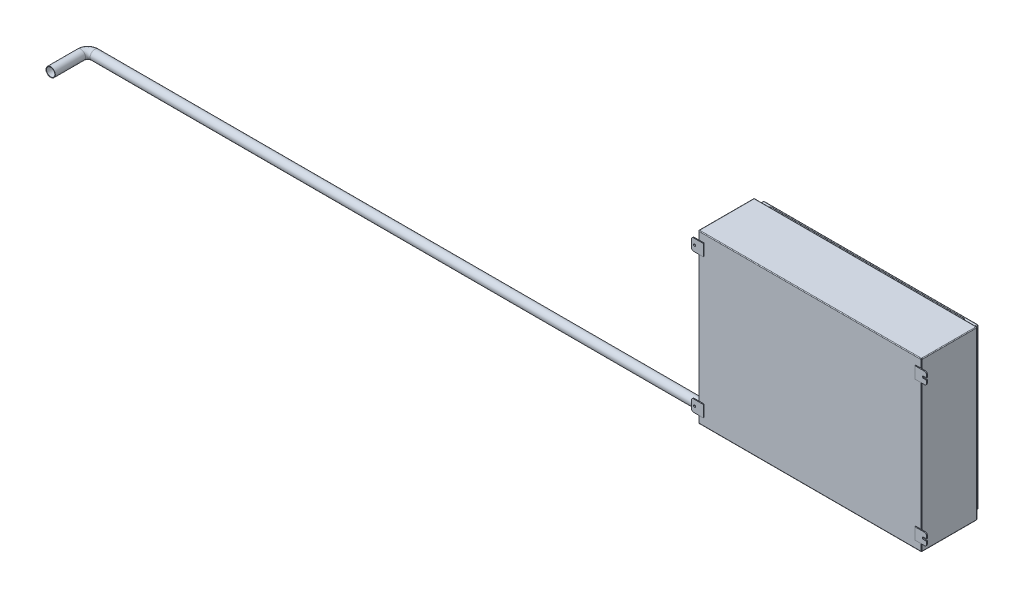
SolidWorks part; units mm, degrees
ref_plane "Front Plane" through (0, 0, 0) normal (0, 0, 1) x (1, 0, 0)
ref_plane "Top Plane" through (0, 0, 0) normal (0, 1, 0) x (1, 0, 0)
ref_plane "Right Plane" through (0, 0, 0) normal (1, 0, 0) x (0, 0, -1)
sketch "Sketch1" plane through (0, 0, 0) normal (0, 0, 1) x (1, 0, 0)
  line L0 (-609.6, -457.2) -> (609.6, 457.2) construction
  line L1 (-609.6, 457.2) -> (609.6, 457.2)
  line L2 (-609.6, 457.2) -> (-609.6, -457.2)
  line L3 (-609.6, -457.2) -> (609.6, -457.2)
  line L4 (609.6, 457.2) -> (609.6, -457.2)
  line L5 (-607.7026, 455.3026) -> (-607.7026, -455.3026)
  line L6 (-607.7026, -455.3026) -> (607.7026, -455.3026)
  line L7 (607.7026, 455.3026) -> (607.7026, -455.3026)
  line L8 (-607.7026, 455.3026) -> (607.7026, 455.3026)
  line L9 (571.5, -419.1) -> (-571.5, 419.1) construction
  line L10 (-571.5, 419.1) -> (571.5, 419.1)
  line L11 (-571.5, 419.1) -> (-571.5, -419.1)
  line L12 (-571.5, -419.1) -> (571.5, -419.1)
  line L13 (571.5, 419.1) -> (571.5, -419.1)
  line L14 (-549.275, 396.875) -> (-549.275, -396.875) construction
  line L15 (-549.275, -396.875) -> (549.275, -396.875) construction
  line L16 (549.275, 396.875) -> (549.275, -396.875) construction
  line L17 (-549.275, 396.875) -> (549.275, 396.875) construction
  line L18 (609.6, 412.75) -> (641.35, 412.75)
  line L19 (641.35, 412.75) -> (641.35, 386.5562)
  line L21 (-641.35, 349.25) -> (-609.6, 349.25)
  line L22 (0, 0) -> (0, 396.875) construction
  line L23 (-609.6, 412.75) -> (-641.35, 412.75)
  line L25 (-641.35, 412.75) -> (-641.35, 349.25)
  line L26 (0, 0) -> (0, 125.3343) construction
  line L27 (-544.5125, 396.875) -> (-544.5125, -396.875) construction
  line L28 (625.475, 375.4437) -> (609.6, 375.4437) construction
  line L29 (-625.475, 381) -> (-625.475, 349.25) construction
  line L30 (641.35, 349.25) -> (609.6, 349.25)
  line L31 (625.475, 375.4437) -> (641.35, 375.4437)
  line L32 (625.475, 386.5562) -> (641.35, 386.5562)
  line L33 (641.35, 375.4437) -> (641.35, 349.25)
  line L34 (625.475, 381) -> (625.475, 412.75) construction
  line L35 (-625.475, 365.125) -> (-609.6, 365.125) construction
  line L36 (0, 0) -> (571.5, 0) construction
  line L37 (-625.475, 381) -> (625.475, 381) construction
  line L38 (-641.35, -349.25) -> (-609.6, -349.25)
  line L39 (-641.35, -412.75) -> (-641.35, -349.25)
  line L40 (-609.6, -412.75) -> (-641.35, -412.75)
  line L41 (641.35, -349.25) -> (609.6, -349.25)
  line L42 (641.35, -375.4437) -> (641.35, -349.25)
  line L43 (625.475, -375.4437) -> (641.35, -375.4437)
  line L44 (641.35, -412.75) -> (641.35, -386.5562)
  line L45 (625.475, -386.5562) -> (641.35, -386.5562)
  line L46 (609.6, -412.75) -> (641.35, -412.75)
  circle A0 centre (549.275, 396.875) radius 4.7625 construction
  circle A1 centre (549.275, -396.875) radius 4.7625 construction
  circle A2 centre (-549.275, -396.875) radius 4.7625 construction
  circle A3 centre (-549.275, 396.875) radius 4.7625 construction
  circle A4 centre (-625.475, 381) radius 5.5563
  arc A6 (625.475, 386.5562) -> (625.475, 375.4437) centre (625.475, 381) ccw
  circle A12 centre (-625.475, -381) radius 5.5563
  arc A13 (625.475, -386.5562) -> (625.475, -375.4437) centre (625.475, -381) cw
  circle A14 centre (0, 396.875) radius 4.7625 construction
  circle A15 centre (0, -396.875) radius 4.7625 construction
  dimension "panel screw hole" = 9.525
  dimension "D6" = 11.1125
  dimension "D1" = 63.5
  dimension "D3" = 1250.95
  dimension "D2" = 22.225
sketch "Sketch2" plane through (0, 0, 0) normal (0, 1, 0) x (1, 0, 0)
  line L0 (-609.6, -152.4) -> (609.6, 152.4) construction
  line L1 (-609.6, 152.4) -> (609.6, 152.4)
  line L2 (-609.6, 152.4) -> (-609.6, -152.4)
  line L3 (-609.6, -152.4) -> (609.6, -152.4)
  line L4 (609.6, 152.4) -> (609.6, -152.4)
  line L5 (-607.7026, 150.5026) -> (-607.7026, -150.5026)
  line L6 (-571.5, -122.8166) -> (571.5, -122.8166)
  line L7 (-571.5, -122.8166) -> (-571.5, -125.4735)
  line L8 (-571.5, -125.4735) -> (571.5, -125.4735)
  line L9 (571.5, -122.8166) -> (571.5, -125.4735)
  line L10 (-607.7026, -150.5026) -> (607.7026, -150.5026)
  line L11 (607.7026, 150.5026) -> (607.7026, -150.5026)
  line L12 (-607.7026, 150.5026) -> (607.7026, 150.5026)
  line L13 (-609.6, 152.4) -> (609.6, 152.4) construction
  line L14 (-574.675, 152.4) -> (-574.675, 150.5026) construction
  line L15 (574.675, 152.4) -> (574.675, 150.5026) construction
  line L16 (-586.613, 173.482) -> (586.613, 173.482) construction
  line L17 (0, 0) -> (0, 173.482) construction
  line L18 (-586.613, 179.9666) -> (586.613, 179.9666) construction
  line L19 (-577.85, -152.4) -> (577.85, -152.4) construction
  line L20 (-641.35, -152.4) -> (-577.85, -152.4)
  line L21 (-641.35, -152.4) -> (-641.35, -157.226)
  line L22 (-641.35, -157.226) -> (-577.85, -157.226)
  line L23 (-577.85, -152.4) -> (-577.85, -157.226)
  line L24 (577.85, -152.4) -> (641.35, -152.4)
  line L25 (577.85, -152.4) -> (577.85, -157.226)
  line L26 (577.85, -157.226) -> (641.35, -157.226)
  line L27 (641.35, -152.4) -> (641.35, -157.226)
  line L28 (0, 0) -> (0, -152.4) construction
  line L29 (-586.613, 181.864) -> (586.613, 181.864) construction
  line L30 (-577.0499, 152.4) -> (-577.0499, 150.5026) construction
  dimension "D4" = 34.925
  dimension "P" = 1173.226
  dimension "D6" = 4.826
  dimension "D2" = 27.686
  dimension "D7" = 1.8974
  dimension "D8" = 29.464
  dimension "D9" = 63.5
  dimension "D10" = 32.5501
  dimension "D3" = 34.925
  dimension "D5" = 21.082
  dimension "D1" = 1.8974
sketch "Sketch4" plane through (0, 0, 0) normal (0, 0, 1) x (1, 0, 0)
  line L1 (-609.6, -457.2) -> (609.6, -457.2) construction
  line L2 (609.6, 457.2) -> (609.6, -457.2) construction
  line L4 (-609.6, 457.2) -> (609.6, 457.2) construction
  line L7 (-609.6, 457.2) -> (-609.6, -457.2) construction
  line L9 (-609.6, -457.2) -> (609.6, -457.2)
  line L10 (609.6, 457.2) -> (609.6, -457.2)
  line L12 (-609.6, 457.2) -> (609.6, 457.2)
  line L15 (-609.6, 457.2) -> (-609.6, -457.2)
extrude "Extrude1" add sketch "Sketch4" along normal mid plane 304.8
sketch "Sketch27" plane through (0, 0, -152.4) normal (0, 0, -1) x (-1, 0, 0)
  line L0 (609.6, 457.2) -> (609.6, -457.2) construction
  line L1 (574.675, -422.275) -> (-574.675, -422.275) construction
  line L2 (574.675, -422.275) -> (574.675, 422.275) construction
  line L3 (574.675, 422.275) -> (-574.675, 422.275) construction
  line L4 (-574.675, -422.275) -> (-574.675, 422.275) construction
  line L5 (609.6, 457.2) -> (-609.6, 457.2) construction
  line L10 (609.6, -457.2) -> (-609.6, -457.2) construction
  line L11 (578.4698, -426.0698) -> (-578.4698, -426.0698)
  line L12 (-578.4698, -426.0698) -> (-578.4698, 426.0698)
  line L13 (578.4698, 426.0698) -> (-578.4698, 426.0698)
  line L14 (578.4698, -426.0698) -> (578.4698, 426.0698)
  dimension "D1" = 34.925
  dimension "D2" = 34.925
  dimension "D3" = 34.925
  dimension "D4" = 3.7948
extrude "Extrude19" add sketch "Sketch27" along normal up to vertex (21.082 mm away) up to point (586.613, 0, -173.482)
fillet "Fillet1" radius 3.7948 20 edges at (609.6, -457.2, 0) (0, -457.2, -152.4) (609.6, 0, -152.4) (609.6, 0, 152.4) (0, -457.2, 152.4) (609.6, 457.2, 0) (0, 457.2, 152.4) (0, 457.2, -152.4) (-609.6, 457.2, 0) (-609.6, 0, 152.4) (-609.6, -457.2, 0) (-609.6, 0, -152.4) (0, 426.0698, -152.4) (578.4698, 0, -152.4) (0, -426.0698, -152.4) (-578.4698, 0, -152.4) (578.4698, -426.0698, -162.941) (578.4698, 426.0698, -162.941) (-578.4698, 426.0698, -162.941) (-578.4698, -426.0698, -162.941)
shell "Shell1" thickness 1.8974
sketch "Sketch5" plane through (0, 0, -173.482) normal (0, 0, -1) x (-1, 0, 0)
  line L8 (-576.5724, 422.275) -> (-576.5724, -422.275)
  line L9 (574.675, 424.1724) -> (-574.675, 424.1724)
  line L10 (576.5724, -422.275) -> (576.5724, 422.275)
  line L11 (-574.675, -424.1724) -> (574.675, -424.1724)
  line L12 (-576.5724, 422.275) -> (-576.5724, -422.275)
  line L13 (574.675, 424.1724) -> (-574.675, 424.1724)
  line L14 (576.5724, -422.275) -> (576.5724, 422.275)
  line L15 (-574.675, -424.1724) -> (574.675, -424.1724)
  arc A4 (-574.675, 424.1724) -> (-576.5724, 422.275) centre (-574.675, 422.275) ccw
  arc A5 (576.5724, 422.275) -> (574.675, 424.1724) centre (574.675, 422.275) ccw
  arc A6 (574.675, -424.1724) -> (576.5724, -422.275) centre (574.675, -422.275) ccw
  arc A7 (-576.5724, -422.275) -> (-574.675, -424.1724) centre (-574.675, -422.275) ccw
  arc A8 (-574.675, 424.1724) -> (-576.5724, 422.275) centre (-574.675, 422.275) ccw
  arc A9 (576.5724, 422.275) -> (574.675, 424.1724) centre (574.675, 422.275) ccw
  arc A10 (574.675, -424.1724) -> (576.5724, -422.275) centre (574.675, -422.275) ccw
  arc A11 (-576.5724, -422.275) -> (-574.675, -424.1724) centre (-574.675, -422.275) ccw
  dimension "D1" = 0
extrude "Cut-Extrude1" cut sketch "Sketch5" against normal blind 1.8974
sketch "Sketch50" plane through (0, 0, -152.4) normal (0, 0, -1) x (-1, 0, 0)
  line L0 (-609.6, 0) -> (-582.2645, 0) construction
  line L1 (-582.2645, -422.275) -> (-582.2645, 422.275) construction
  line L2 (-609.6, -453.4052) -> (-609.6, 453.4052) construction
  dimension "D1" = 27.3355
sketch "Sketch6" plane through (0, 0, 152.4) normal (0, 0, 1) x (1, 0, 0)
  line L6 (-641.35, 349.25) -> (-609.6, 349.25) construction
  line L7 (-609.6, 412.75) -> (-641.35, 412.75) construction
  line L8 (-641.35, 412.75) -> (-641.35, 349.25) construction
  line L9 (-641.35, 349.25) -> (-609.6, 349.25)
  line L10 (-609.6, 412.75) -> (-641.35, 412.75)
  line L11 (-641.35, 412.75) -> (-641.35, 349.25)
  line L12 (641.35, 349.25) -> (609.6, 349.25) construction
  line L13 (641.35, 375.4437) -> (641.35, 349.25) construction
  line L14 (625.475, 375.4437) -> (641.35, 375.4437) construction
  line L15 (625.475, 386.5562) -> (641.35, 386.5562) construction
  line L16 (641.35, 412.75) -> (641.35, 386.5562) construction
  line L17 (609.6, 412.75) -> (641.35, 412.75) construction
  line L18 (641.35, 349.25) -> (609.6, 349.25)
  line L19 (641.35, 375.4437) -> (641.35, 349.25)
  line L20 (625.475, 375.4437) -> (641.35, 375.4437)
  line L21 (625.475, 386.5562) -> (641.35, 386.5562)
  line L22 (641.35, 412.75) -> (641.35, 386.5562)
  line L23 (609.6, 412.75) -> (641.35, 412.75)
  line L24 (-609.6, 412.75) -> (-577.85, 412.75)
  line L25 (-577.85, 412.75) -> (-577.85, 349.25)
  line L26 (-609.6, 349.25) -> (-577.85, 349.25)
  line L27 (609.6, 412.75) -> (577.85, 412.75)
  line L28 (577.85, 412.75) -> (577.85, 349.25)
  line L29 (609.6, 349.25) -> (577.85, 349.25)
  line L30 (0, 0) -> (609.6, 0) construction
  line L31 (609.6, 457.2) -> (609.6, -457.2) construction
  line L32 (609.6, -349.25) -> (577.85, -349.25)
  line L33 (577.85, -412.75) -> (577.85, -349.25)
  line L34 (609.6, -412.75) -> (577.85, -412.75)
  line L35 (-609.6, -349.25) -> (-577.85, -349.25)
  line L36 (-577.85, -412.75) -> (-577.85, -349.25)
  line L37 (-609.6, -412.75) -> (-577.85, -412.75)
  line L38 (609.6, -412.75) -> (641.35, -412.75)
  line L39 (641.35, -412.75) -> (641.35, -386.5562)
  line L40 (625.475, -386.5562) -> (641.35, -386.5562)
  line L41 (625.475, -375.4437) -> (641.35, -375.4437)
  line L42 (641.35, -375.4437) -> (641.35, -349.25)
  line L43 (641.35, -349.25) -> (609.6, -349.25)
  line L44 (-641.35, -412.75) -> (-641.35, -349.25)
  line L45 (-609.6, -412.75) -> (-641.35, -412.75)
  line L46 (-641.35, -349.25) -> (-609.6, -349.25)
  circle A7 centre (-625.475, 381) radius 5.5563 construction
  circle A8 centre (-625.475, 381) radius 5.5563
  arc A9 (625.475, 386.5562) -> (625.475, 375.4437) centre (625.475, 381) ccw construction
  arc A10 (625.475, 386.5562) -> (625.475, 375.4437) centre (625.475, 381) ccw
  arc A11 (625.475, -386.5562) -> (625.475, -375.4437) centre (625.475, -381) cw
  circle A12 centre (-625.475, -381) radius 5.5563
extrude "Extrude2" add sketch "Sketch6" along normal up to vertex (4.826 mm away) up to point (641.35, 0, 157.226)
sketch "Sketch16" plane through (0, 0, 150.5026) normal (0, 0, -1) x (-1, 0, 0)
  circle A0 centre (-549.275, 396.875) radius 8.3344
  circle A1 centre (549.275, 396.875) radius 8.3344
  circle A2 centre (549.275, -396.875) radius 8.3344
  circle A3 centre (-549.275, -396.875) radius 8.3344
  circle A4 centre (-549.275, 396.875) radius 4.7625 construction
  circle A5 centre (-549.275, -396.875) radius 4.7625 construction
  circle A6 centre (549.275, -396.875) radius 4.7625 construction
  circle A7 centre (0, 396.875) radius 8.3344
  circle A8 centre (-549.275, 396.875) radius 4.7625
  circle A9 centre (-549.275, -396.875) radius 4.7625
  circle A10 centre (549.275, -396.875) radius 4.7625
  circle A13 centre (549.275, 396.875) radius 4.7625
  circle A16 centre (0, 396.875) radius 4.7625 construction
  circle A17 centre (0, 396.875) radius 4.7625
  circle A18 centre (0, -396.875) radius 8.3344
  circle A19 centre (0, -396.875) radius 4.7625 construction
  circle A20 centre (0, -396.875) radius 4.7625
  dimension "D1" = 16.6688
  dimension "D2" = 9.525
extrude "Extrude6" add sketch "Sketch16" along normal up to vertex (25.0292 mm away) up to point (571.5, 0, 125.4735)
sketch "Sketch17" plane through (0, 0, 150.5026) normal (0, 0, -1) x (-1, 0, 0)
  circle A1 centre (-549.275, 396.875) radius 4.7625
  circle A2 centre (-549.275, 396.875) radius 4.7625
  circle A5 centre (0, -396.875) radius 4.7625 construction
  circle A6 centre (0, -396.875) radius 4.7625
  circle A11 centre (549.275, 396.875) radius 4.7625
  circle A12 centre (549.275, 396.875) radius 4.7625
  circle A13 centre (549.275, -396.875) radius 4.7625
  circle A14 centre (549.275, -396.875) radius 4.7625
  circle A15 centre (-549.275, -396.875) radius 4.7625
  circle A16 centre (-549.275, -396.875) radius 4.7625
  circle A20 centre (0, 396.875) radius 4.7625 construction
  circle A21 centre (0, 396.875) radius 4.7625
  dimension "D1" = 0
  dimension "D6" = 0
  dimension "D7" = 0
  dimension "D8" = 0
extrude "Extrude7" add sketch "Sketch17" along normal offset from surface (40.9042 mm away) 15.875 up to face at (540.9406, 396.875, 125.4735) offset beyond the face yes
sketch "Sketch18" plane through (0, 0, 125.4735) normal (0, 0, -1) x (-1, 0, 0)
  line L0 (571.5, -419.1) -> (-571.5, -419.1) construction
  line L1 (571.5, 419.1) -> (571.5, -419.1) construction
  line L2 (571.5, 419.1) -> (-571.5, 419.1) construction
  line L3 (-571.5, 419.1) -> (-571.5, -419.1) construction
  line L4 (571.5, -419.1) -> (-571.5, -419.1)
  line L5 (571.5, 419.1) -> (571.5, -419.1)
  line L6 (571.5, 419.1) -> (-571.5, 419.1)
  line L7 (-571.5, 419.1) -> (-571.5, -419.1)
  circle A1 centre (549.275, 396.875) radius 5.5245
  circle A2 centre (549.275, -396.875) radius 5.5245
  circle A3 centre (549.275, -396.875) radius 5.5245
  circle A4 centre (-549.275, 396.875) radius 5.5245
  circle A5 centre (-549.275, -396.875) radius 5.5245
  dimension "D1" = 0.762
extrude "Extrude8" add sketch "Sketch18" along normal up to vertex (2.6568 mm away) up to point (571.5, 0, 122.8166)
ref_plane "Plane1" through (0, 0, -181.864) normal (0, 0, 1) x (1, 0, 0)
sketch "Sketch7" plane through (0, 0, -181.864) normal (0, 0, 1) x (1, 0, 0)
  line L0 (-609.6, 457.2) -> (609.6, 457.2) construction
  line L1 (-586.613, 441.198) -> (586.613, 441.198)
  line L2 (-586.613, 441.198) -> (-586.613, -431.8)
  line L3 (-586.613, -431.8) -> (586.613, -431.8)
  line L4 (586.613, 441.198) -> (586.613, -431.8)
  line L5 (-609.6, -457.2) -> (609.6, -457.2) construction
  line L6 (0, 0) -> (0, -431.8) construction
  line L7 (-609.6, -457.2) -> (609.6, 457.2) construction
  dimension "D1" = 872.998
  dimension "D2" = 25.4
  dimension "D3" = 16.002
  dimension "D4" = 1173.226
extrude "Extrude3" add sketch "Sketch7" along normal blind 17.4625 separate body
fillet "Fillet2" radius 3.7948 8 edges at (0, -431.8, -181.864) (586.613, 4.699, -181.864) (0, 441.198, -181.864) (-586.613, 4.699, -181.864) (-586.613, -431.8, -173.1327) (-586.613, 441.198, -173.1327) (586.613, -431.8, -173.1327) (586.613, 441.198, -173.1327)
shell "Shell2" thickness 1.8974 removed face at (0, 4.699, -164.4015)
ref_plane "Plane2" through (0, 437.4032, 0) normal (0, 1, 0) x (-1, 0, 0)
sketch "Sketch8" plane through (0, 437.4032, 0) normal (0, 1, 0) x (-1, 0, 0)
  line L0 (-586.613, -164.4015) -> (-584.7156, -164.4015)
  line L1 (-584.7156, -164.4015) -> (-584.7156, -163.3753)
  line L2 (-588.0177, -160.9663) -> (-593.0976, -162.5947)
  line L3 (-593.0976, -162.5947) -> (-592.5184, -164.4015)
  line L4 (-592.5184, -164.4015) -> (-587.4385, -162.7731)
  line L5 (-586.613, -164.4015) -> (-586.613, -163.3753)
  line L7 (-586.613, -164.4015) -> (-586.613, -178.0692) construction
  line L8 (582.8182, -164.4015) -> (-582.8182, -164.4015) construction
  line L10 (-190.1607, -160.8455) -> (-179.6224, -160.8455) construction
  arc A0 (-584.7156, -163.3753) -> (-588.0177, -160.9663) centre (-587.2455, -163.3753) ccw
  arc A1 (-587.4385, -162.7731) -> (-586.613, -163.3753) centre (-587.2455, -163.3753) cw
  dimension "D5" = 0.6325
  dimension "D4" = 1.8974
  dimension "D2" = 8.382
  dimension "D3" = 3.556
sketch "Sketch9" plane through (0, 0, -164.4015) normal (0, 0, 1) x (1, 0, 0)
  line L0 (586.613, -428.0052) -> (586.613, 437.4032) construction
  line L1 (-582.8182, -431.8) -> (582.8182, -431.8) construction
  line L2 (586.613, -428.0052) -> (586.613, 437.4032)
  line L3 (-582.8182, -431.8) -> (582.8182, -431.8)
  line L4 (-586.613, 437.4032) -> (-586.613, -428.0052) construction
  line L5 (-586.613, 437.4032) -> (-586.613, -428.0052)
  arc A0 (582.8182, -431.8) -> (586.613, -428.0052) centre (582.8182, -428.0052) ccw construction
  arc A1 (582.8182, -431.8) -> (586.613, -428.0052) centre (582.8182, -428.0052) ccw
  arc A2 (-586.613, -428.0052) -> (-582.8182, -431.8) centre (-582.8182, -428.0052) ccw construction
  arc A3 (-586.613, -428.0052) -> (-582.8182, -431.8) centre (-582.8182, -428.0052) ccw
sweep "Sweep1" add profiles "Sketch8" path "Sketch9"
sketch "Sketch10" plane through (0, 0, -164.4015) normal (0, 0, 1) x (1, 0, 0)
  line L1 (-654.9517, 519.8491) -> (654.9517, 519.8491)
  line L2 (-654.9517, 519.8491) -> (-654.9517, 392.8491)
  line L3 (-654.9517, 392.8491) -> (654.9517, 392.8491)
  line L4 (654.9517, 519.8491) -> (654.9517, 392.8491)
  line L5 (-654.9517, -392.8491) -> (-527.9517, -392.8491)
  line L6 (-654.9517, -392.8491) -> (-654.9517, -519.8491)
  line L7 (-654.9517, -519.8491) -> (-527.9517, -519.8491)
  line L8 (-527.9517, -392.8491) -> (-527.9517, -519.8491)
  line L9 (527.9517, -392.8491) -> (654.9517, -392.8491)
  line L10 (527.9517, -392.8491) -> (527.9517, -519.8491)
  line L11 (527.9517, -519.8491) -> (654.9517, -519.8491)
  line L12 (654.9517, -392.8491) -> (654.9517, -519.8491)
  line L14 (-591.4517, -392.8491) -> (-591.4517, 392.8491) construction
  line L17 (-591.4517, 0) -> (0, 0) construction
  line L18 (-527.9517, -456.3491) -> (527.9517, -456.3491) construction
  line L19 (0, -456.3491) -> (0, 0) construction
  dimension "D5" = 127
  dimension "D1" = 785.6982
  dimension "D2" = 1055.9034
extrude "Cut-Extrude2" cut sketch "Sketch10" along normal blind 12.7 draft 30 draft outward yes
sketch "Sketch11" plane through (0, 0, -181.864) normal (0, 0, -1) x (-1, 0, 0)
  line L0 (527.0115, -432.6255) -> (528.0589, -438.2846)
  line L1 (528.0589, -438.2846) -> (523.7442, -438.2846)
  line L2 (527.0115, -432.6255) -> (523.7442, -438.2846)
  line L3 (527.0115, -432.6255) -> (527.9517, -437.7054) construction
  line L4 (-526.9085, -438.2846) -> (526.9085, -438.2846) construction
  line L5 (587.4385, -391.9089) -> (593.0976, -392.9563)
  line L6 (593.0976, -392.9563) -> (593.0976, -388.6416)
  line L7 (593.0976, -388.6416) -> (587.4385, -391.9089)
  line L8 (592.5184, -392.8491) -> (587.4385, -391.9089) construction
  line L9 (593.0976, -391.8059) -> (593.0976, 391.8059) construction
  line L10 (592.5184, 0) -> (16.547, 0) construction
  line L11 (592.5184, -392.8491) -> (592.5184, 392.8491) construction
  line L12 (593.0976, 388.6416) -> (587.4385, 391.9089)
  line L13 (593.0976, 392.9563) -> (593.0976, 388.6416)
  line L14 (587.4385, 391.9089) -> (593.0976, 392.9563)
  line L15 (0, -437.7054) -> (0, -6.7093) construction
  line L16 (-527.9517, -437.7054) -> (527.9517, -437.7054) construction
  line L17 (-587.4385, 391.9089) -> (-593.0976, 392.9563)
  line L18 (-593.0976, 392.9563) -> (-593.0976, 388.6416)
  line L19 (-593.0976, 388.6416) -> (-587.4385, 391.9089)
  line L20 (-593.0976, -388.6416) -> (-587.4385, -391.9089)
  line L21 (-593.0976, -392.9563) -> (-593.0976, -388.6416)
  line L22 (-587.4385, -391.9089) -> (-593.0976, -392.9563)
  line L23 (-527.0115, -432.6255) -> (-523.7442, -438.2846)
  line L24 (-528.0589, -438.2846) -> (-523.7442, -438.2846)
  line L25 (-527.0115, -432.6255) -> (-528.0589, -438.2846)
  ellipse E0 centre (527.3592, -432.4325) end of major axis (527.3592, -433.0649) minor radius 0.3652 (527.3592, -431.8) -> (527.0115, -432.6255) ccw construction
  ellipse E1 centre (587.2455, -392.2566) end of major axis (587.8779, -392.2566) minor radius 0.3652 (587.4385, -391.9089) -> (586.613, -392.2566) ccw construction
  dimension "D1" = 60
  dimension "D2" = 60
extrude "Cut-Extrude3" cut sketch "Sketch11" against normal through all
sketch "Sketch12" plane through (0, 0, 0) normal (1, 0, 0) x (0, 0, -1)
  line L1 (163.4528, 447.8788) -> (163.4528, 439.3006) construction
  line L2 (163.4528, 439.3006) -> (178.0692, 439.3006) construction
  line L3 (178.0692, 439.3006) -> (178.0692, 437.4032) construction
  line L4 (178.0692, 437.4032) -> (161.5554, 437.4032) construction
  line L5 (161.5554, 437.4032) -> (161.5554, 443.7109) construction
  line L7 (178.0692, 439.3006) -> (164.4015, 439.3006) construction
  line L8 (152.4, 447.8788) -> (152.4, 429.8645)
  line L9 (152.4, 429.8645) -> (154.2974, 429.8645)
  line L10 (154.2974, 429.8645) -> (154.2974, 443.7109)
  line L11 (154.2974, 443.7109) -> (157.9264, 447.8788) construction
  line L12 (154.2974, 443.7109) -> (154.2974, 447.8788)
  line L13 (155.9499, 444.8353) -> (154.6959, 443.395)
  line L16 (178.0692, 437.4032) -> (178.0692, -428.0052) construction
  line L17 (148.6052, 453.4052) -> (-148.6052, 453.4052) construction
  line L18 (164.4015, 441.198) -> (164.4015, 437.4032) construction
  line L19 (152.4, 453.4052) -> (152.4, -453.4052) construction
  arc A4 (155.9499, 444.8353) -> (154.2974, 447.8788) centre (157.9264, 447.8788) ccw
  arc A5 (154.6959, 443.395) -> (152.4, 447.8788) centre (157.9264, 447.8788) ccw
  dimension "D1" = 1.8974
  dimension "D4" = 1.8974
  dimension "D3" = 0.508
  dimension "D2" = 0.9487
extrude "Extrude4" add sketch "Sketch12" along normal mid plane 1055.9034 separate body
sketch "Sketch13" plane through (0, 0, 0) normal (1, 0, 0) x (0, 0, -1)
  line L0 (179.9666, 439.3006) -> (163.4528, 439.3006)
  line L1 (163.4528, 447.8788) -> (163.4528, 439.3006) construction
  line L2 (161.5554, 437.4032) -> (161.5554, 443.7109) construction
  line L3 (179.9666, 439.3006) -> (179.9666, 437.4032)
  line L4 (179.9666, 437.4032) -> (161.5554, 437.4032)
  line L5 (163.4528, 447.8788) -> (163.4528, 439.3006)
  line L6 (161.5554, 437.4032) -> (161.5554, 443.7109)
  line L10 (178.0692, 439.3006) -> (164.4015, 439.3006) construction
  line L13 (179.9666, -428.0052) -> (179.9666, 437.4032) construction
  line L14 (152.4, 429.8645) -> (154.2974, 429.8645) construction
  arc A0 (163.4528, 447.8788) -> (161.5554, 443.7109) centre (157.9264, 447.8788) ccw
  arc A1 (154.6959, 443.395) -> (152.4, 447.8788) centre (157.9264, 447.8788) ccw construction
  circle A2 centre (157.9264, 447.8788) radius 3.629
  arc A4 (155.9499, 444.8353) -> (154.2974, 447.8788) centre (157.9264, 447.8788) ccw construction
extrude "Extrude5" add sketch "Sketch13" along normal mid plane 1055.9034 separate body
sketch "Sketch14" plane through (0, 306.3189, -152.4) normal (0, 0, 1) x (1, 0, 0)
  line L1 (-21.1181, 147.0863) -> (21.1181, 147.0863)
  line L2 (-21.1181, 147.0863) -> (-21.1181, 134.7635)
  line L3 (-21.1181, 134.7635) -> (21.1181, 134.7635)
  line L4 (21.1181, 147.0863) -> (21.1181, 134.7635)
  line L5 (527.9517, 147.0863) -> (-527.9517, 147.0863) construction
  line L7 (527.9517, 123.5456) -> (-527.9517, 123.5456) construction
  line L8 (0, -306.3189) -> (0, 134.7635) construction
  line L9 (-527.9517, 136.0335) -> (527.9517, 136.0335) construction
  dimension "D1" = 1055.9034
  dimension "D2" = 42.2361
  dimension "D3" = 1.27
extrude "Cut-Extrude4" cut sketch "Sketch14" against normal mid plane 25.4
pattern_linear "LPattern1" count 8 spacing 84.4723 along (-1, 0, 0) count 8 spacing 84.4723 along (1, 0, 0) of "Cut-Extrude4"
sketch "Sketch15" plane through (0, 216.0613, -161.5554) normal (0, 0, 1) x (1, 0, 0)
  line L0 (-21.1181, 225.0211) -> (21.1181, 225.0211) construction
  line L1 (-63.3542, 225.9101) -> (-21.1181, 225.9101)
  line L2 (-63.3542, 225.9101) -> (-63.3542, 237.3439)
  line L3 (-63.3542, 237.3439) -> (-21.1181, 237.3439)
  line L4 (-21.1181, 225.9101) -> (-21.1181, 237.3439)
  line L7 (527.9517, 237.3439) -> (-527.9517, 237.3439) construction
  line L8 (-527.9517, 226.2911) -> (527.9517, 226.2911) construction
  dimension "D1" = 0.381
extrude "Cut-Extrude5" cut sketch "Sketch15" along normal through all and the other way through all
pattern_linear "LPattern2" count 8 spacing 84.4723 along (-1, 0, 0) count 8 spacing 84.4723 along (1, 0, 0) of "Cut-Extrude5"
combine bodies "Combine1" operation type add bodies to combine 113 107
combine bodies "Combine2" operation type add bodies to combine 118 111
sketch "Sketch28" plane through (527.9517, 0, 0) normal (1, 0, 0) x (0, 0, -1)
  circle A0 centre (157.9264, 447.8788) radius 3.629
  circle A1 centre (157.9264, 447.8788) radius 3.629 construction
extrude "Extrude20" add sketch "Sketch28" against normal up to surface (1055.9034 mm away) separate body up to face at (-527.9517, 447.8788, -161.5554)
ref_plane "Plane3" through (571.5, 0, 0) normal (1, 0, 0) x (0, 0, -1)
ref_plane "Plane5" through (-0.254, 0, 0) normal (1, 0, 0) x (0, 0, -1)
sketch "Sketch29" plane through (-0.254, 0, 0) normal (1, 0, 0) x (0, 0, -1)
  line L0 (178.0692, -431.8) -> (164.2745, -431.8)
  line L1 (164.2745, -431.8) -> (164.2745, -453.4052)
  line L2 (178.0692, -431.8) -> (178.0692, -433.6974)
  line L3 (178.0692, -433.6974) -> (166.1719, -433.6974)
  line L4 (166.1719, -433.6974) -> (166.1719, -453.4052)
  line L5 (164.2745, -453.4052) -> (166.1719, -453.4052)
  line L6 (178.0692, -431.8) -> (164.4015, -431.8) construction
  line L7 (152.4, -453.4052) -> (148.6052, -453.4052) construction
  dimension "D1" = 1.8974
  dimension "D2" = 0.127
extrude "Extrude21" add sketch "Sketch29" along normal mid plane 53.975 separate body
fillet "Fillet6" radius 6.35 4 edges at (26.7335, -432.7487, -178.0692) (-27.2415, -432.7487, -178.0692) (-27.2415, -453.4052, -165.2232) (26.7335, -453.4052, -165.2232)
fillet "Fillet7" radius 2.032 1 edges at (-0.254, -431.8, -164.2745)
fillet "Fillet8" radius 0.254 1 edges at (-0.254, -433.6974, -166.1719)
sketch "Sketch30" plane through (0, 0, -166.1719) normal (0, 0, -1) x (-1, 0, 0)
  line L0 (0.254, -453.4052) -> (0.254, -450.2302) construction
  line L1 (12.554, -443.0801) -> (-12.0459, -443.0801)
  line L2 (-20.3835, -453.4052) -> (20.8915, -453.4052) construction
  line L3 (12.554, -450.2302) -> (-12.0459, -450.2302)
  arc A0 (12.554, -443.0801) -> (12.554, -450.2302) centre (12.554, -446.6552) cw
  arc A1 (-12.0459, -443.0801) -> (-12.0459, -450.2302) centre (-12.0459, -446.6552) ccw
  dimension "D1" = 31.75
  dimension "D2" = 7.1501
  dimension "D3" = 3.175
extrude "Cut-Extrude6" cut sketch "Sketch30" against normal up to vertex (1.8974 mm away) up to point (26.7335, -433.832, -164.2745)
ref_plane "Plane6" through (0, -446.6552, 0) normal (0, 1, 0) x (-1, 0, 0)
sketch "Sketch31" plane through (0, -446.6552, 0) normal (0, 1, 0) x (-1, 0, 0)
  line L0 (0.254, -164.2745) -> (0.254, -175.0619) construction
  line L1 (-6.096, -184.5869) -> (6.604, -184.5869)
  line L2 (-12.446, -178.2369) -> (-12.446, -152.4)
  line L3 (-12.446, -152.4) -> (12.954, -152.4)
  line L4 (12.954, -178.2369) -> (12.954, -152.4)
  line L5 (-605.8052, -152.4) -> (605.8052, -152.4) construction
  line L6 (-20.3835, -164.2745) -> (20.8915, -164.2745) construction
  line L8 (0.254, -181.4119) -> (0.254, -184.5869) construction
  circle A0 centre (0.254, -175.0619) radius 6.35
  arc A1 (6.604, -184.5869) -> (12.954, -178.2369) centre (6.604, -178.2369) ccw
  arc A2 (-6.096, -184.5869) -> (-12.446, -178.2369) centre (-6.096, -178.2369) cw
  point P15 (12.954, -184.5869)
  point P19 (-12.446, -184.5869)
  dimension "D3" = 12.7
  dimension "D4" = 2.54
  dimension "D5" = 6.35
  dimension "D1" = 25.4
  dimension "D2" = 3.175
extrude "Extrude22" add sketch "Sketch31" along normal mid plane 2.032 separate body
sketch "Sketch32" plane through (0, -447.6712, 0) normal (0, -1, 0) x (1, 0, 0)
  line L0 (-12.954, -178.2369) -> (-12.954, -152.4) construction
  line L1 (12.446, -152.4) -> (-12.954, -152.4)
  line L2 (12.446, -152.4) -> (12.446, -154.432)
  line L3 (12.446, -154.432) -> (-12.954, -154.432)
  line L4 (-12.954, -152.4) -> (-12.954, -154.432)
  dimension "D1" = 2.032
extrude "Extrude23" add sketch "Sketch32" against normal blind 15.875
fillet "Fillet11" radius 9.525 8 edges at (641.35, -349.25, 154.813) (641.35, 349.25, 154.813) (641.35, 412.75, 154.813) (641.35, -412.75, 154.813) (-641.35, -412.75, 154.813) (-641.35, -349.25, 154.813) (-641.35, 412.75, 154.813) (-641.35, 349.25, 154.813)
combine bodies "Combine6" operation type add bodies to combine 162 114
sketch "Sketch33" plane through (0, 0, -152.4) normal (0, 0, -1) x (-1, 0, 0)
  line L1 (13.6677, 28.575) -> (-13.6677, 28.575)
  line L2 (13.6677, 28.575) -> (13.6677, 15.875)
  line L3 (13.6677, -28.575) -> (-13.6677, -28.575)
  line L4 (-13.6677, 28.575) -> (-13.6677, -28.575)
  line L6 (13.6677, 15.875) -> (-0.9677, 15.875)
  line L7 (-0.9677, 15.875) -> (-0.9677, -15.875)
  line L8 (-0.9677, -15.875) -> (13.6677, -15.875)
  line L9 (13.6677, -15.875) -> (13.6677, -28.575)
  line L10 (-13.6677, 0) -> (-0.9677, 0) construction
  line L11 (0, -28.575) -> (0, 0) construction
  dimension "D1" = 57.15
  dimension "D2" = 12.7
  dimension "D3" = 27.3355
extrude "Extrude24" [suppressed] add sketch "Sketch33" along normal blind 2.032 separate body
sketch "Sketch34" [suppressed] plane through (0, 0, -154.432) normal (0, 0, -1) x (-1, 0, 0)
  line L1 (-13.6677, 10.4775) -> (-0.9677, 10.4775)
  line L2 (-13.6677, 10.4775) -> (-13.6677, -10.4775)
  line L3 (-13.6677, -10.4775) -> (-0.9677, -10.4775)
  line L4 (-0.9677, 10.4775) -> (-0.9677, -10.4775)
  line L5 (-0.9677, -15.875) -> (-0.9677, 15.875) construction
  line L6 (-13.6677, 0) -> (-0.9677, 0) construction
  line L7 (-13.6677, 28.575) -> (-13.6677, -28.575) construction
  dimension "D1" = 20.955
extrude "Extrude25" [suppressed] add sketch "Sketch34" along normal blind 12.065
sketch "Sketch35" [suppressed] plane through (13.6677, 0, 0) normal (1, 0, 0) x (0, 0, -1)
  line L0 (166.497, 10.4775) -> (154.432, 10.4775) construction
  line L1 (152.4, 7.3025) -> (163.322, 7.3025)
  line L2 (152.4, 7.3025) -> (152.4, -7.3025)
  line L3 (152.4, -7.3025) -> (163.322, -7.3025)
  line L4 (163.322, 7.3025) -> (163.322, -7.3025)
  line L5 (166.497, 10.4775) -> (166.497, -10.4775) construction
  line L6 (166.497, -10.4775) -> (154.432, -10.4775) construction
  line L7 (152.4, 28.575) -> (152.4, -28.575) construction
  dimension "D1" = 3.175
  dimension "D2" = 3.175
  dimension "D3" = 3.175
extrude "Cut-Extrude7" [suppressed] cut sketch "Sketch35" against normal through all
fillet "Fillet9" [suppressed] radius 2.032
fillet "Fillet10" [suppressed] radius 4.064
sketch "Sketch36" [suppressed] plane through (0, 0, -166.497) normal (0, 0, -1) x (-1, 0, 0)
  line L0 (-13.6677, -6.4135) -> (-0.9677, 6.4135) construction
  circle A0 centre (-7.3177, 0) radius 3.175
  dimension "D1" = 6.35
extrude "Cut-Extrude8" [suppressed] cut sketch "Sketch36" against normal through all
ref_plane "Plane7" [suppressed] through (0, 0, 0) normal (0, 1, 0) x (-1, 0, 0)
sketch "Sketch37" [suppressed] plane through (0, 0, 0) normal (0, 1, 0) x (-1, 0, 0)
  line L0 (6.176, -162.5041) -> (6.176, -173.6166)
  line L1 (1.4135, -178.3791) -> (-16.049, -178.3791)
  line L2 (-20.8115, -173.6166) -> (-20.8115, -160.2816)
  line L3 (-16.049, -155.5191) -> (-7.3177, -155.5191)
  line L4 (-7.3177, -166.497) -> (-7.3177, -178.3791) construction
  line L5 (-10.4927, -166.497) -> (-4.1427, -166.497) construction
  arc A0 (6.176, -173.6166) -> (1.4135, -178.3791) centre (1.4135, -173.6166) cw
  arc A1 (-16.049, -178.3791) -> (-20.8115, -173.6166) centre (-16.049, -173.6166) cw
  arc A2 (-20.8115, -160.2816) -> (-16.049, -155.5191) centre (-16.049, -160.2816) cw
  point P11 (6.176, -178.3791)
  point P14 (-20.8115, -178.3791)
  dimension "D3" = 4.7625
  dimension "D4" = 15.875
  dimension "D1" = 26.9875
  dimension "D2" = 22.86
  dimension "D5" = 11.8821
extrude "Extrude-Thin1" [suppressed] add sketch "Sketch37" along normal mid plane 31.75 separate body thin thin type one direction wall 2.54
sketch "Sketch38" [suppressed] plane through (0, 0, -155.5191) normal (0, 0, 1) x (1, 0, 0)
  line L0 (13.6677, 5.2705) -> (0.9677, 5.2705) construction
  line L1 (7.3177, 15.875) -> (20.8115, 15.875)
  line L2 (7.3177, 15.875) -> (7.3177, 5.2705)
  line L3 (7.3177, 5.2705) -> (20.8115, 5.2705)
  line L4 (20.8115, 15.875) -> (20.8115, 5.2705)
  line L5 (7.3177, -5.2705) -> (20.8115, -5.2705)
  line L6 (7.3177, -5.2705) -> (7.3177, -15.875)
  line L7 (7.3177, -15.875) -> (20.8115, -15.875)
  line L8 (20.8115, -5.2705) -> (20.8115, -15.875)
  line L9 (0.9677, -5.2705) -> (13.6677, -5.2705) construction
  line L10 (7.3177, 15.875) -> (7.3177, -15.875) construction
extrude "Cut-Extrude9" [suppressed] cut sketch "Sketch38" against normal up to vertex up to point (0, 20.8115, -15.875)
sketch "Sketch39" [suppressed] plane through (0, 0, -175.8391) normal (0, 0, 1) x (1, 0, 0)
  line L0 (1.7615, 3.175) -> (12.874, 3.175)
  line L1 (1.7615, -3.175) -> (12.874, -3.175)
  line L2 (-1.4135, 15.875) -> (-1.4135, -15.875) construction
  line L3 (16.049, 15.875) -> (16.049, -15.875) construction
  arc A0 (1.7615, 3.175) -> (1.7615, -3.175) centre (1.7615, 0) ccw
  arc A1 (12.874, -3.175) -> (12.874, 3.175) centre (12.874, 0) ccw
  circle A2 centre (7.3177, 0) radius 3.175 construction
extrude "Cut-Extrude10" [suppressed] cut sketch "Sketch39" against normal through all
sketch "Sketch40" [suppressed] plane through (0, 0, -158.0591) normal (0, 0, -1) x (-1, 0, 0)
  circle A3 centre (-7.3177, 0) radius 3.048
  circle A4 centre (-7.3177, 0) radius 3.048
  dimension "D1" = 0.127
extrude "Extrude27" [suppressed] add sketch "Sketch40" along normal up to surface (20.32 mm away)
sketch "Sketch41" [suppressed] plane through (0, 0, -178.3791) normal (0, 0, -1) x (-1, 0, 0)
  circle A0 centre (-7.3177, 0) radius 6.35
  circle A1 centre (-7.3177, 0) radius 3.048 construction
  dimension "D1" = 12.7
extrude "Extrude28" [suppressed] add sketch "Sketch41" along normal blind 1.143
sketch "Sketch42" [suppressed] plane through (0, 0, -179.5221) normal (0, 0, -1) x (-1, 0, 0)
  line L0 (-13.6677, -6.4135) -> (-0.9677, 6.4135) construction
  line L1 (-7.3177, 5.4993) -> (-12.0802, 2.7496)
  line L2 (-12.0802, 2.7496) -> (-12.0802, -2.7496)
  line L3 (-12.0802, -2.7496) -> (-7.3177, -5.4993)
  line L4 (-7.3177, -5.4993) -> (-2.5552, -2.7496)
  line L5 (-2.5552, -2.7496) -> (-2.5552, 2.7496)
  line L6 (-2.5552, 2.7496) -> (-7.3177, 5.4993)
  circle A0 centre (-7.3177, 0) radius 4.7625 construction
  dimension "D1" = 9.525
extrude "Extrude29" [suppressed] add sketch "Sketch42" along normal blind 4.7625
sketch "Sketch43" [suppressed] plane through (0, 0, -184.2846) normal (0, 0, -1) x (-1, 0, 0)
  circle A0 centre (-7.3177, 0) radius 4.7625 construction
  circle A1 centre (-7.3177, 0) radius 4.7625
extrude "Cut-Extrude11" [suppressed] cut sketch "Sketch43" against normal blind 2.54 draft 60 flip side to cut
sketch "Sketch44" [suppressed] plane through (0, 0, -184.2846) normal (0, 0, -1) x (-1, 0, 0)
  circle A2 centre (-7.3177, 0) radius 4.3815
  circle A3 centre (-7.3177, 0) radius 4.3815
  dimension "D1" = 0.381
extrude "Cut-Extrude12" [suppressed] cut sketch "Sketch44" against normal blind 0.762 draft 20
sketch "Sketch45" [suppressed] plane through (0, 0, -184.2846) normal (0, 0, -1) x (-1, 0, 0)
  line L0 (-11.8302, 4.4677) -> (-2.8053, -4.4677)
  line L1 (-13.6677, -6.4135) -> (-0.9677, 6.4135) construction
  circle A0 centre (-7.3177, 0) radius 6.35 construction
  arc A1 (-12.817, -3.175) -> (-1.8185, -3.175) centre (-7.3177, 0) ccw construction
  dimension "D1" = 90
extrude "Cut-Extrude-Thin1" [suppressed] cut sketch "Sketch45" against normal blind 1.778 thin thin type mid plane wall 1.778
sketch "Sketch46" [suppressed] plane through (0, 0, -166.497) normal (0, 0, -1) x (-1, 0, 0)
  line L4 (-13.6677, 6.4135) -> (-13.6677, -6.4135)
  line L5 (-13.6677, -6.4135) -> (-0.9677, -6.4135)
  line L6 (-0.9677, -6.4135) -> (-0.9677, 6.4135)
  line L7 (-0.9677, 6.4135) -> (-13.6677, 6.4135)
  line L8 (-13.6677, 6.4135) -> (-13.6677, -6.4135)
  line L9 (-13.6677, -6.4135) -> (-0.9677, -6.4135)
  line L10 (-0.9677, -6.4135) -> (-0.9677, 6.4135)
  line L11 (-0.9677, 6.4135) -> (-13.6677, 6.4135)
  dimension "D1" = 0
extrude "Extrude30" [suppressed] add sketch "Sketch46" against normal blind 0.508
sketch "Sketch47" [suppressed] plane through (0, 0, 0) normal (1, 0, 0) x (0, 0, -1)
  line L0 (0, 0) -> (178.3791, 0) construction
  line L1 (178.3791, 0) -> (178.3791, -15.875) construction
ref_axis "Axis1" through (0, 0, -173.482) along (0, 0, 1)
pattern_circular "CirPattern1" [suppressed] count 2 over 90 about axis through (0, 0, -173.482) along (0, 0, 1) of bodies 179
sketch "Sketch48" [suppressed] plane through (0, 0, -154.432) normal (0, 0, -1) x (-1, 0, 0)
  line L0 (-13.6677, -20.5422) -> (-609.6, -20.5423) construction
  line L1 (-13.6677, -12.5095) -> (-13.6677, -28.575) construction
  line L2 (-609.6, -453.4052) -> (-609.6, 453.4052) construction
  line L3 (-609.6, -20.5423) -> (-609.6, -371.348) construction
  line L4 (605.8052, -457.2) -> (-605.8052, -457.2) construction
  dimension "D1" = 595.9323
  dimension "D2" = 85.852
  dimension "D3" = 350.8058
sketch "Sketch49" [suppressed] plane through (0, 0, -154.432) normal (0, 0, -1) x (-1, 0, 0)
  line L0 (0, -13.6677) -> (0, -457.2) construction
  line L1 (0, -457.2) -> (-523.748, -457.2) construction
  line L2 (605.8052, -457.2) -> (-605.8052, -457.2) construction
  line L3 (-609.6, -453.4052) -> (-609.6, 453.4052) construction
  line L4 (-28.575, -13.6677) -> (-12.5095, -13.6677) construction
  point P10 (-261.874, -457.2)
  dimension "D1" = 85.852
  dimension "D2" = 443.5323
  dimension "D3" = 523.748
  dimension "D4" = 261.874
pattern_linear "LPattern7" [suppressed] count 2 spacing 595.9323 of bodies 179
mirror "Mirror4" [suppressed] about plane through (0, 0, 0) normal (1, 0, 0) of bodies 195
pattern_linear "LPattern8" [suppressed] count 2 spacing 443.5323 count 2 spacing 261.874 of bodies 180
pattern_linear "LPattern3" [suppressed] count 2 spacing 595.9323 of bodies 179
delete or keep bodies "Body-Delete1" [suppressed] type delete bodies bodies 179
pattern_linear "LPattern4" [suppressed] count 2 spacing 443.5323 count 2 spacing 523.748 of bodies 180
delete or keep bodies "Body-Delete2" [suppressed] type delete bodies bodies 180
mirror "Mirror1" [suppressed] about plane through (0, 0, 0) normal (1, 0, 0) of bodies 182 181
pattern_linear "LPattern5" [suppressed] count 2 spacing 595.9323 along (1, 0, 0) count 2 spacing 350.8058 along (0, -1, 0) of bodies 179 180
pattern_linear "LPattern6" [suppressed] count 2 spacing 443.5323 along (0, -1, 0) count 2 spacing 523.748 along (1, 0, 0) of bodies 180
mirror "Mirror2" [suppressed] about plane through (0, 0, 0) normal (0, 1, 0) of bodies 188
mirror "Mirror3" [suppressed] about plane through (0, 0, 0) normal (1, 0, 0) of bodies 190 188 194 189
delete or keep bodies "Body-Delete3" [suppressed] type delete bodies bodies 180 179
mirror "Mirror5" [suppressed] about plane through (0, 0, 0) normal (1, 0, 0) of bodies 197
delete or keep bodies "Body-Delete4" [suppressed] type delete bodies bodies 189
sketch "Sketch51" plane through (0, 0, -181.864) normal (0, 0, -1) x (-1, 0, 0)
  line L0 (71.5032, 413.5303) -> (71.5032, -428.0052) construction
  line L2 (-582.8182, -428.0052) -> (582.8182, -428.0052) construction
  text T0 "LIGHT DRIVERS \r\nENCLOSURE" font "Arial" height in points 300
extrude "Cut-Extrude13" cut sketch "Sketch51" against normal blind 0.508
sketch "Sketch52" plane through (-609.6, 0, 0) normal (-1, 0, 0) x (0, 0, 1)
  line L1 (-148.6052, -453.4052) -> (148.6052, -453.4052) construction
  line L2 (148.6052, -453.4052) -> (148.6052, 453.4052) construction
  line L3 (87.6452, -402.6052) -> (85.1052, -402.6052) construction
  circle A0 centre (110.5052, -402.6052) radius 25.4
  circle A1 centre (110.5052, -402.6052) radius 22.86
  dimension "D1" = 50.8
  dimension "D2" = 50.8
  dimension "D3" = 38.1
  dimension "D4" = 2.54
extrude "Boss-Extrude1" add sketch "Sketch52" along normal blind 3302 separate body
ref_axis "Axis2" through (-3911.6, -402.6052, 110.5052) along (1, 0, 0)
ref_plane "Plane8" through (0, -402.6052, 0) normal (0, 1, 0) x (1, 0, 0)
sketch "Sketch54" plane through (-3911.6, 0, 0) normal (-1, 0, 0) x (0, 0, 1)
  circle A0 centre (110.5052, -402.6052) radius 22.86 construction
  circle A1 centre (110.5052, -402.6052) radius 22.86
  circle A2 centre (110.5052, -402.6052) radius 25.4 construction
  circle A3 centre (110.5052, -402.6052) radius 25.4
sketch "Sketch53" plane through (0, -402.6052, 0) normal (0, 1, 0) x (1, 0, 0)
  line L0 (-3911.6, -110.5052) -> (-3949.7, -110.5052)
  line L1 (-3987.8, -148.6052) -> (-3987.8, -313.7052)
  arc A0 (-3949.7, -110.5052) -> (-3987.8, -148.6052) centre (-3949.7, -148.6052) ccw
  point P6 (-3987.8, -110.5052)
  dimension "D3" = 38.1
  dimension "D1" = 76.2
  dimension "D2" = 203.2
sweep "Sweep2" add profiles "Sketch54" path "Sketch53"
equation "\"D1@Sketch2\" = \"thickness@Sketch1\""
equation "\"D1@Extrude1\" = \"D@Sketch2\""
equation "\"D1@Fillet1\" = \"thickness@Sketch1\"*2"
equation "\"D1@Shell1\" = \"thickness@Sketch1\""
equation "\"D1@Cut-Extrude1\" = \"thickness@Sketch1\""
equation "\"D1@Fillet2\" = \"D1@Fillet1\""
equation "\"D1@Shell2\" = \"thickness@Sketch1\""
equation "\"D4@Sketch8\" = \"thickness@Sketch1\""
equation "\"D5@Sketch8\" = \"D4@Sketch8\"/3"
equation "\"D3@LPattern1\" = \"D2@Sketch14\"*2"
equation "\"D4@LPattern1\" = \"D3@LPattern1\""
equation "\"D4@LPattern2\" = \"D3@LPattern1\""
equation "\"D3@LPattern2\" = \"D4@LPattern2\""
equation "\"D3@Sketch1\" = \"H@Sketch1\"+1.250"
equation "\"P@Sketch2\" = \"H@Sketch1\"-1.81"
equation "\"D1@Sketch7\" = \"W@Sketch1\"-1.63"
equation "\"D4@Sketch7\" = \"H@Sketch1\"-1.81"
equation "\"D7@Sketch2\" = \"D1@Sketch2\""
equation "\"D4@Sketch12\" = \"thickness@Sketch1\""
equation "\"D1@Extrude4\" = \"D4@Sketch7\"*.9"
equation "\"D1@Extrude5\" = \"D1@Extrude4\""
equation "\"D3@Sketch27\" = \"D2@Sketch27\""
equation "\"D4@Sketch27\" = \"thickness@Sketch1\"*2"
equation "\"D1@Sketch10\" = \"D1@Sketch7\"*.9"
equation "\"D2@Sketch10\" = \"D4@Sketch7\"*.9"
equation "\"D1@Sketch12\" = \"D4@Sketch12\""
equation "\"D2@Sketch12\" = \"D4@Sketch12\"/2"
equation "\"D1@Sketch29\" = \"thickness@Sketch1\""
equation "\"D3@LPattern4\" = \"D2@Sketch49\""
equation "\"D4@LPattern4\" = \"D3@Sketch49\""
equation "\"D4@LPattern5\" = \"D3@Sketch48\""
equation "\"D3@LPattern5\" = \"D1@Sketch48\""
equation "\"D3@LPattern6\" = \"D2@Sketch49\""
equation "\"D4@LPattern6\" = \"D3@Sketch49\""
equation "\"D3@LPattern7\" = \"D1@Sketch48\""
equation "\"D4@LPattern8\" = \"D4@Sketch49\""
equation "\"D3@LPattern8\" = \"D2@Sketch49\""
